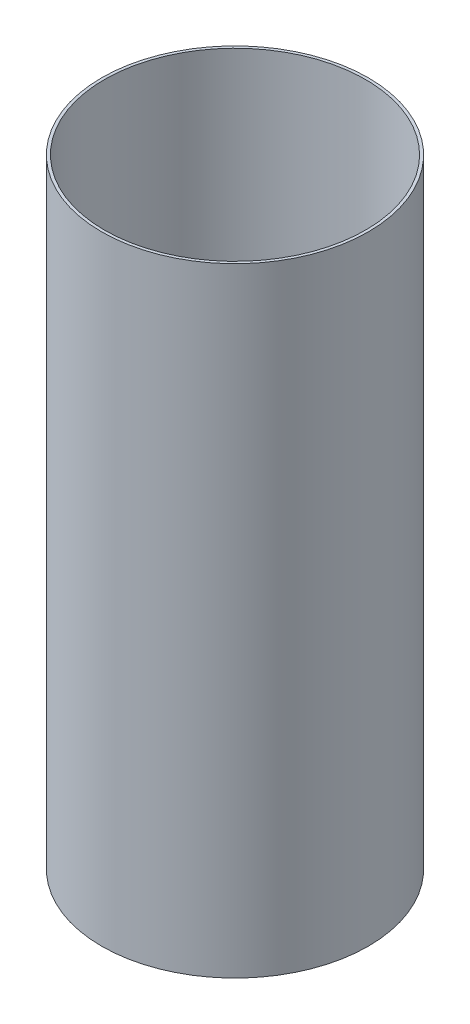
SolidWorks part; units mm, degrees
material "A-Glass Fiber"
ref_plane "Front Plane" through (0, 0, 0) normal (0, 0, 1) x (1, 0, 0)
ref_plane "Top Plane" through (0, 0, 0) normal (0, 1, 0) x (1, 0, 0)
ref_plane "Right Plane" through (0, 0, 0) normal (1, 0, 0) x (0, 0, -1)
sketch "Sketch1" plane through (0, 0, 0) normal (0, 1, 0) x (1, 0, 0)
  circle A0 centre (0, 0) radius 78.35
  circle A1 centre (0, 0) radius 76.67
  dimension "D1" = 156.7
  dimension "D2" = 1.68
extrude "Boss-Extrude1" add sketch "Sketch1" along normal blind 181.7 and the other way blind 181.7
